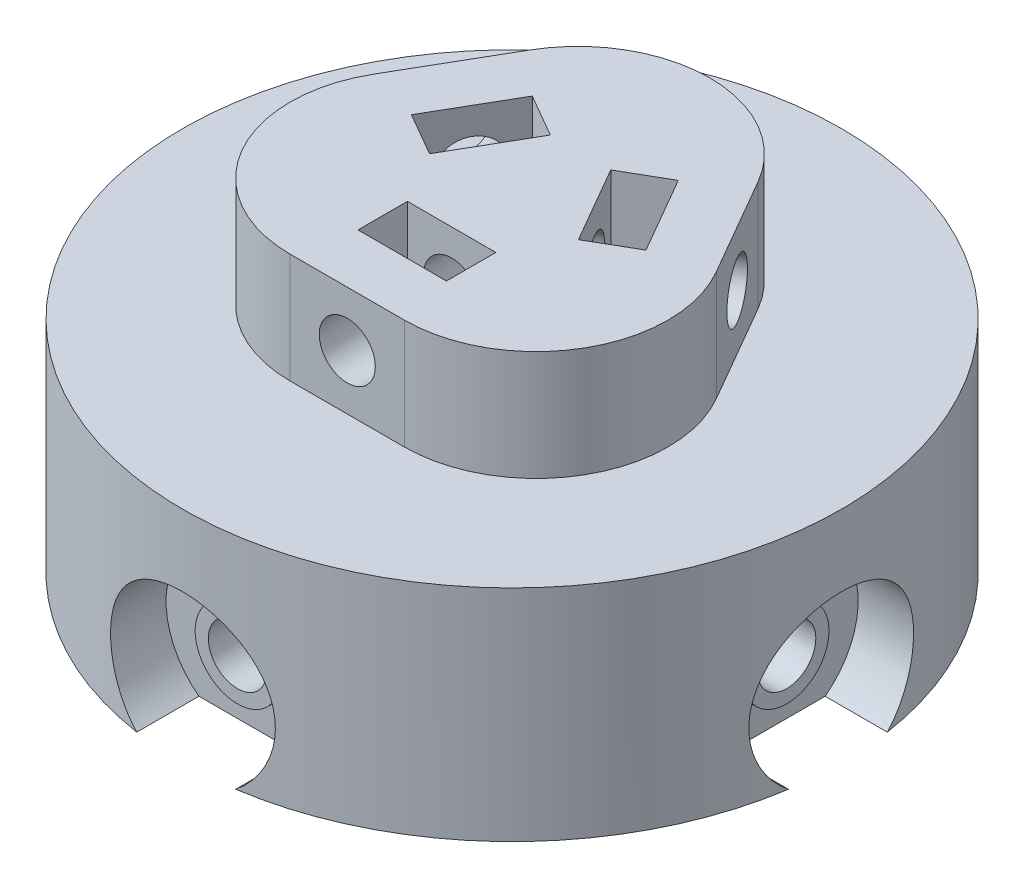
SolidWorks part; units mm, degrees
ref_plane "Front Plane" through (0, 0, 0) normal (0, 0, 1) x (1, 0, 0)
ref_plane "Top Plane" through (0, 0, 0) normal (0, 1, 0) x (1, 0, 0)
ref_plane "Right Plane" through (0, 0, 0) normal (1, 0, 0) x (0, 0, -1)
sketch "Sketch1" plane through (0, 0, 0) normal (0, 1, 0) x (1, 0, 0)
  circle A0 centre (0, 0) radius 30
  dimension "D1" = 60
extrude "Boss-Extrude1" add sketch "Sketch1" along normal blind 20
shell "Shell1" thickness 4
sketch "Sketch2" plane through (0, 0, 0) normal (0, -1, 0) x (1, 0, 0)
  circle A0 centre (0, 0) radius 20.15
  dimension "D1" = 40.3
extrude "Cut-Extrude1" cut sketch "Sketch2" against normal up to next
ref_plane "Plane1" through (-30, 0, 0) normal (-1, 0, 0) x (0, 0, 1)
sketch "Sketch7" plane through (-30, 0, 0) normal (-1, 0, 0) x (0, 0, 1)
  line L0 (-30, 0) -> (30, 0) construction
  line L1 (-8, 0) -> (8, 0)
  line L2 (-8, 0) -> (-8, 11)
  line L3 (-3, 16) -> (3, 16)
  line L4 (8, 0) -> (8, 11)
  arc A0 (3, 16) -> (8, 11) centre (3, 11) cw
  arc A1 (-8, 11) -> (-3, 16) centre (-3, 11) cw
  point P6 (0, 0)
  point P10 (8, 16)
  point P13 (-8, 16)
  dimension "D3" = 5
  dimension "D1" = 16
  dimension "D2" = 16
extrude "Boss-Extrude2" add sketch "Sketch7" against normal up to surface (9.5061 mm away) from offset 2 up to face at (0, 4, 20.15) offset against normal yes
sketch "Sketch3" plane through (-30, 0, -30) normal (1, 0, 0) x (0, 0, -1)
  circle A0 centre (-30, 6) radius 7.5
  dimension "D1" = 15
  dimension "D2" = 6
extrude "Cut-Extrude2" cut sketch "Sketch3" along normal blind 5 contours A0
sketch "Sketch5" plane through (-30, 0, 0) normal (-1, 0, 0) x (0, 0, 1)
  circle A0 centre (0, 6) radius 2.65
  arc A2 (4.5, 0) -> (-4.5, 0) centre (0, 6) ccw construction
  dimension "D1" = 5.3
extrude "Cut-Extrude4" cut sketch "Sketch5" against normal up to next
sketch "Sketch8" plane through (-25, 0, 0) normal (-1, 0, 0) x (0, 0, 1)
  line L0 (-4.5, 0) -> (4.5, 0)
  arc A0 (4.5, 0) -> (-4.5, 0) centre (0, 6) ccw construction
  arc A1 (4.5, 0) -> (-4.5, 0) centre (0, 6) ccw
  circle A5 centre (0, 6) radius 3.85
  dimension "D1" = 7.7
extrude "Cut-Extrude6" cut sketch "Sketch8" against normal blind 1
pattern_circular "CirPattern1" count 4 over 360 of "Cut-Extrude2", "Cut-Extrude4", "Cut-Extrude6", "Boss-Extrude2"
ref_plane "Plane2" through (0, 35, 0) normal (0, 1, 0) x (1, 0, 0)
sketch "Sketch9" plane through (0, 35, 0) normal (0, 1, 0) x (1, 0, 0)
  circle A4 centre (0, 0) radius 45
  dimension "D1" = 90
ref_plane "Plane3" through (0, 55, 0) normal (0, 1, 0) x (1, 0, 0)
sketch "Sketch13" plane through (0, 55, 0) normal (0, 1, 0) x (1, 0, 0)
  circle A6 centre (0, 0) radius 60
  dimension "D1" = 120
sketch "Sketch10" plane through (0, 20, 0) normal (0, 1, 0) x (1, 0, 0)
  circle A4 centre (0, 0) radius 30
  circle A5 centre (0, 0) radius 30
  dimension "D1" = 0
loft "Loft-Thin1" [suppressed] add profiles "Sketch10", "Sketch9", "Sketch13" parameters "D1"=4
ref_axis "x-as" through (33, 0, 0) along (-1, 0, 0)
ref_axis "Axis1" through (-33, 20, 0) along (1, 0, 0)
ref_axis "Axis2" through (0, 20, 0) along (0, -1, 0)
ref_point "Point1"
sketch "Sketch14" plane through (0, 20, 0) normal (0, 1, 0) x (1, 0, 0)
  line L7 (0, 30) -> (-25.9808, -15)
  line L8 (-25.9808, -15) -> (25.9808, -15)
  line L9 (25.9808, -15) -> (0, 30)
  circle A3 centre (0, 0) radius 15 construction
  circle A5 centre (0, 0) radius 30 construction
extrude "Boss-Extrude3" add sketch "Sketch14" along normal blind 10
sketch "Sketch16" plane through (-12.9904, 0, -7.5) normal (-0.866, 0, -0.5) x (-0.5, 0, 0.866)
  line L0 (25.9808, 30) -> (25.9808, 20) construction
  circle A0 centre (0, 25) radius 2.55
  point P5 (25.9808, 25)
  dimension "D1" = 5.1
extrude "Cut-Extrude7" cut sketch "Sketch16" against normal blind 15
sketch "Sketch17" plane through (-12.9904, 0, -7.5) normal (-0.866, 0, -0.5) x (-0.5, 0, 0.866)
  line L1 (0, 20.3523) -> (4.025, 22.6762)
  line L2 (4.025, 22.6762) -> (4.025, 27.3527)
  line L5 (-4.025, 27.3238) -> (-4.025, 22.6762)
  line L6 (-4.025, 22.6762) -> (0, 20.3523)
  line L7 (-4.025, 27.3238) -> (-4.025, 30)
  line L8 (-25.9808, 30) -> (25.9808, 30) construction
  line L9 (4.025, 30) -> (4.025, 27.3527)
  line L10 (4.025, 30) -> (-4.025, 30)
  line L12 (0.0495, 29.6763) -> (-1.9755, 28.5071) [skipped]
  line L13 (4.0745, 27.2952) -> (2.0495, 28.4644) [skipped]
  arc A0 (-4.025, 25) -> (4.025, 25) centre (0, 25) ccw construction
  dimension "D1" = 8.05
extrude "Cut-Extrude8" cut sketch "Sketch17" against normal blind 4.5 from offset 5 offset against normal yes
pattern_circular "CirPattern2" count 3 over 360 about axis through (0, 20, 0) along (0, -1, 0) of "Cut-Extrude7", "Cut-Extrude8"
fillet "Fillet1" radius 12 3 edges at (-25.9808, 25, 15) (25.9808, 25, 15) (0, 25, -30)
